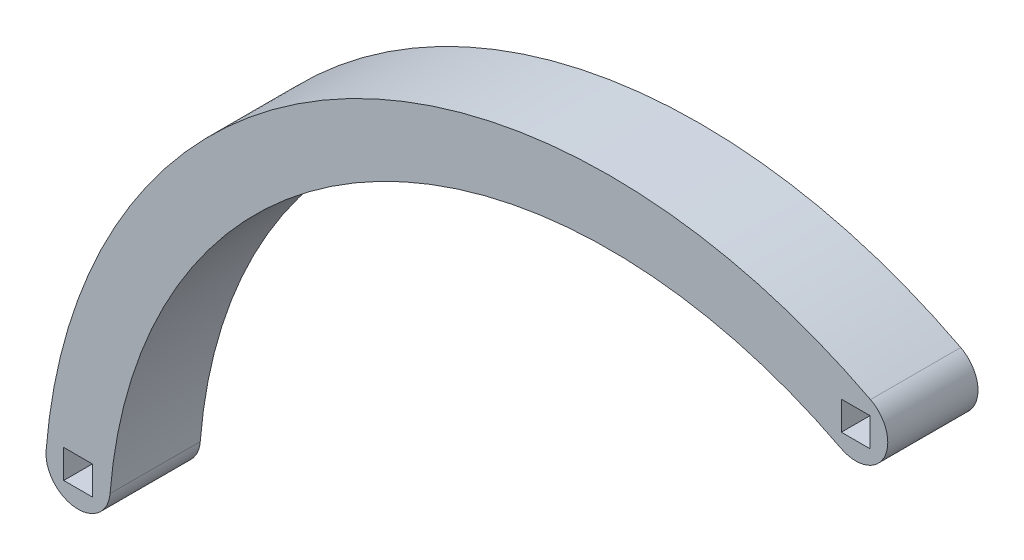
SolidWorks part; units mm, degrees
material "ABS"
ref_plane "Front Plane" through (0, 0, 0) normal (0, 0, 1) x (1, 0, 0)
ref_plane "Top Plane" through (0, 0, 0) normal (0, 1, 0) x (1, 0, 0)
ref_plane "Right Plane" through (0, 0, 0) normal (1, 0, 0) x (0, 0, -1)
sketch "Sketch1" plane through (0, 0, 0) normal (0, 0, 1) x (1, 0, 0)
  line L1 (-1.5875, -1.5875) -> (1.5875, -1.5875)
  line L2 (-1.5875, -1.5875) -> (-1.5875, 1.5875)
  line L3 (-1.5875, 1.5875) -> (1.5875, 1.5875)
  line L4 (1.5875, -1.5875) -> (1.5875, 1.5875)
  line L5 (-1.5875, -1.5875) -> (1.5875, 1.5875) construction
  line L6 (-1.5875, 1.5875) -> (1.5875, -1.5875) construction
  line L7 (84.6057, 46.1432) -> (87.7807, 46.1432)
  line L8 (84.6057, 46.1432) -> (84.6057, 49.3182)
  line L9 (84.6057, 49.3182) -> (87.7807, 49.3182)
  line L10 (87.7807, 46.1432) -> (87.7807, 49.3182)
  line L11 (84.6057, 46.1432) -> (87.7807, 49.3182) construction
  line L12 (84.6057, 49.3182) -> (87.7807, 46.1432) construction
  arc A0 (0, 0) -> (86.1932, 47.7307) centre (58.9334, -4.7332) cw construction
  arc A1 (87.8328, 50.8861) -> (-3.5446, 0.2847) centre (58.9334, -4.7332) ccw
  arc A2 (84.5537, 44.5752) -> (3.5446, -0.2847) centre (58.9334, -4.7332) ccw
  arc A3 (84.5537, 44.5752) -> (87.8328, 50.8861) centre (86.1932, 47.7307) ccw
  arc A4 (-3.5446, 0.2847) -> (3.5446, -0.2847) centre (0, 0) ccw
  point P3 (30.2915, 46.9891)
  point P9 (0, 0)
  point P14 (86.1932, 47.7307)
  dimension "D2" = 3.175
  dimension "D3" = 3.556
  dimension "D1" = 98.5266
extrude "Boss-Extrude1" add sketch "Sketch1" along normal blind 10
